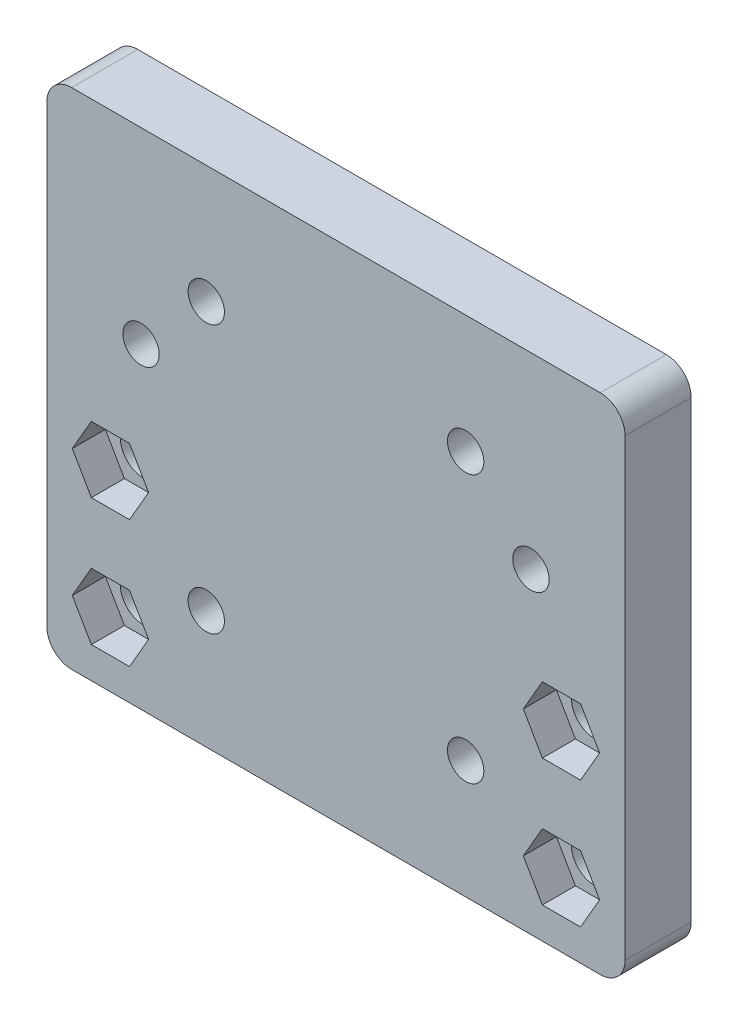
SolidWorks part; units mm, degrees
ref_plane "Front Plane" through (0, 0, 0) normal (0, 0, 1) x (1, 0, 0)
ref_plane "Top Plane" through (0, 0, 0) normal (0, 1, 0) x (1, 0, 0)
ref_plane "Right Plane" through (0, 0, 0) normal (1, 0, 0) x (0, 0, -1)
sketch "Sketch1" plane through (0, 0, 0) normal (0, 0, 1) x (1, 0, 0)
  line L0 (0, 38.735) -> (0, -38.735) construction
  line L1 (40.64, -38.735) -> (-40.64, -38.735)
  line L2 (44.45, -34.925) -> (44.45, 34.925)
  line L3 (40.64, 38.735) -> (-40.64, 38.735)
  line L4 (-44.45, -34.925) -> (-44.45, 34.925)
  line L5 (44.45, -38.735) -> (-44.45, 38.735) construction
  line L6 (44.45, 38.735) -> (-44.45, -38.735) construction
  line L7 (-31.115, -9.271) -> (31.115, -9.271) construction
  line L8 (34.671, -12.827) -> (34.671, -25.273) construction
  line L9 (17.78, 20.574) -> (-17.78, 20.574) construction
  line L10 (44.45, 0) -> (-44.45, 0) construction
  line L11 (17.78, -20.574) -> (-17.78, -20.574) construction
  line L12 (27.813, 9.906) -> (-27.813, 9.906) construction
  circle A0 centre (-34.671, -9.271) radius 3.556
  circle A1 centre (-34.671, -28.829) radius 3.556
  circle A2 centre (34.671, -9.271) radius 3.556
  circle A3 centre (34.671, -28.829) radius 3.556
  arc A4 (44.45, 34.925) -> (40.64, 38.735) centre (40.64, 34.925) ccw
  arc A5 (40.64, -38.735) -> (44.45, -34.925) centre (40.64, -34.925) ccw
  arc A6 (-44.45, -34.925) -> (-40.64, -38.735) centre (-40.64, -34.925) ccw
  arc A7 (-40.64, 38.735) -> (-44.45, 34.925) centre (-40.64, 34.925) ccw
  circle A8 centre (-19.939, 20.574) radius 2.794
  circle A9 centre (19.939, -20.574) radius 2.159 construction
  circle A10 centre (-19.939, -20.574) radius 2.159 construction
  circle A11 centre (19.939, 20.574) radius 2.794
  circle A12 centre (-19.939, 20.574) radius 2.159 construction
  circle A13 centre (19.939, 20.574) radius 2.159 construction
  circle A14 centre (19.939, -20.574) radius 2.794
  circle A15 centre (-19.939, -20.574) radius 2.794
  circle A16 centre (29.972, 9.906) radius 2.159 construction
  circle A17 centre (-29.972, 9.906) radius 2.159 construction
  circle A18 centre (29.972, 9.906) radius 2.794
  circle A19 centre (-29.972, 9.906) radius 2.794
  point P0 (0, 0)
  point P18 (0, -9.271)
  point P21 (0, 0)
  point P48 (0, 20.574)
  point P59 (0, 9.906)
  dimension "D3" = 7.112
  dimension "D4" = 62.23
  dimension "D5" = 12.446
  dimension "D6" = 3.81
  dimension "D7" = 5.588
  dimension "D8" = 35.56
  dimension "D10" = 9.906
  dimension "D11" = 35.56
  dimension "D9" = 4.318
  dimension "D12" = 55.626
  dimension "D13" = 7.747
  dimension "D1" = 88.9
  dimension "D2" = 77.47
extrude "Boss-Extrude1" add sketch "Sketch1" along normal blind 10.16
sketch "Sketch2" plane through (0, 0, 0) normal (0, 0, -1) x (-1, 0, 0)
  line L0 (-44.45, 0) -> (44.45, 0) construction
  line L1 (-44.45, -34.925) -> (-44.45, 34.925) construction
  line L2 (44.45, 34.925) -> (44.45, -34.925) construction
  circle A0 centre (-19.939, 20.574) radius 5.334
  circle A1 centre (19.939, -20.574) radius 5.334
  circle A2 centre (-19.939, -20.574) radius 5.334
  circle A3 centre (19.939, 20.574) radius 5.334
  circle A4 centre (-29.972, 9.906) radius 5.334
  circle A5 centre (29.972, 9.906) radius 5.334
  dimension "D1" = 10.668
extrude "Cut-Extrude1" cut sketch "Sketch2" against normal blind 3.81
sketch "Sketch3" plane through (0, 0, 10.16) normal (0, 0, 1) x (1, 0, 0)
  line L0 (0, 38.735) -> (0, -38.735) construction
  line L1 (-31.7381, -14.351) -> (-28.8051, -9.271)
  line L2 (-28.8051, -9.271) -> (-31.7381, -4.191)
  line L3 (-31.7381, -4.191) -> (-37.6039, -4.191)
  line L4 (-37.6039, -4.191) -> (-40.5369, -9.271)
  line L5 (-40.5369, -9.271) -> (-37.6039, -14.351)
  line L6 (-37.6039, -14.351) -> (-31.7381, -14.351)
  line L7 (-31.7381, -33.909) -> (-28.8051, -28.829)
  line L8 (-28.8051, -28.829) -> (-31.7381, -23.749)
  line L9 (-31.7381, -23.749) -> (-37.6039, -23.749)
  line L10 (-37.6039, -23.749) -> (-40.5369, -28.829)
  line L11 (-40.5369, -28.829) -> (-37.6039, -33.909)
  line L12 (-37.6039, -33.909) -> (-31.7381, -33.909)
  line L13 (40.64, 38.735) -> (-40.64, 38.735) construction
  line L14 (-40.64, -38.735) -> (40.64, -38.735) construction
  line L15 (37.6039, -33.909) -> (31.7381, -33.909)
  line L16 (40.5369, -28.829) -> (37.6039, -33.909)
  line L17 (37.6039, -23.749) -> (40.5369, -28.829)
  line L18 (31.7381, -23.749) -> (37.6039, -23.749)
  line L19 (28.8051, -28.829) -> (31.7381, -23.749)
  line L20 (31.7381, -33.909) -> (28.8051, -28.829)
  line L21 (37.6039, -14.351) -> (31.7381, -14.351)
  line L22 (40.5369, -9.271) -> (37.6039, -14.351)
  line L23 (37.6039, -4.191) -> (40.5369, -9.271)
  line L24 (31.7381, -4.191) -> (37.6039, -4.191)
  line L25 (28.8051, -9.271) -> (31.7381, -4.191)
  line L26 (31.7381, -14.351) -> (28.8051, -9.271)
  circle A0 centre (-34.671, -9.271) radius 5.08 construction
  circle A1 centre (-34.671, -28.829) radius 5.08 construction
  circle A2 centre (34.671, -28.829) radius 5.08 construction
  circle A3 centre (34.671, -9.271) radius 5.08 construction
  dimension "D1" = 10.16
extrude "Cut-Extrude2" cut sketch "Sketch3" against normal blind 5.08
chamfer "Chamfer1" distance 3.81 angle 45 6 edges at (-25.273, 20.574, 0) (-35.306, 9.906, 0) (-14.605, -20.574, 0) (25.273, -20.574, 0) (24.638, 9.906, 0) (14.605, 20.574, 0)
